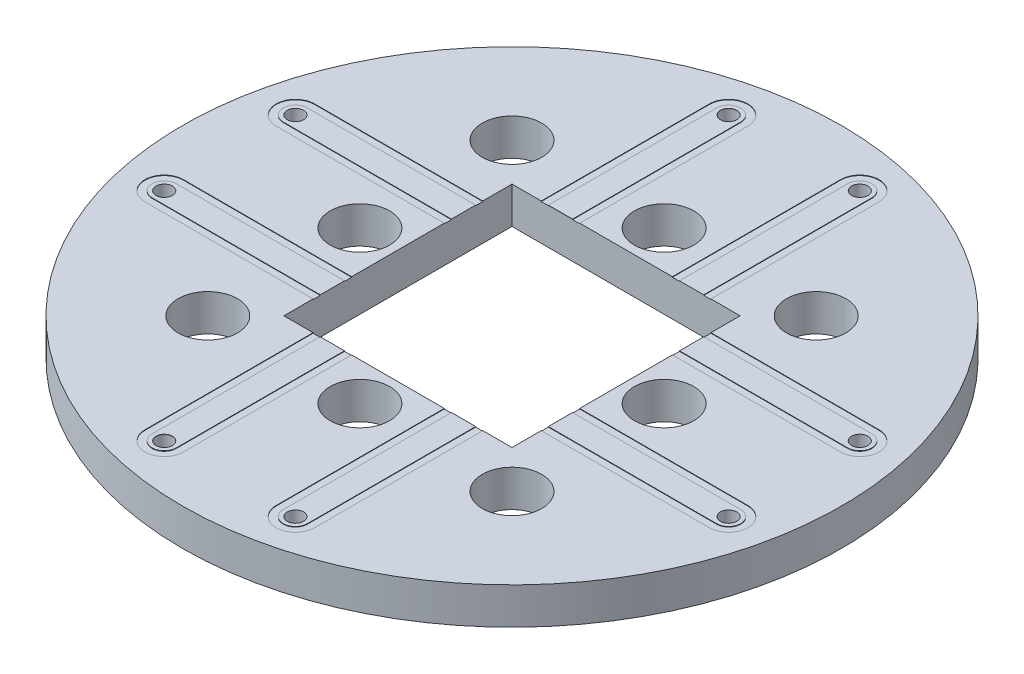
SolidWorks part; units mm, degrees
material "Ceramic Porcelain"
ref_plane "Front Plane" through (0, 0, 0) normal (0, 0, 1) x (1, 0, 0)
ref_plane "Top Plane" through (0, 0, 0) normal (0, 1, 0) x (1, 0, 0)
ref_plane "Right Plane" through (0, 0, 0) normal (1, 0, 0) x (0, 0, -1)
ref_axis "Y Axis" through (0, 0.0762, 0) along (0, -1, 0)
sketch "Boday Sketch" plane through (0, 0, 0) normal (0, 1, 0) x (1, 0, 0)
  circle A0 centre (0, 0) radius 11.557
  dimension "D1" = 23.114
extrude "Body" add sketch "Boday Sketch" against normal blind 1.27
sketch "Copper Sketch" plane through (0, 0, 0) normal (0, 1, 0) x (1, 0, 0)
  circle A0 centre (0, 0) radius 11.557
  dimension "D1" = 23.114
extrude "Copper" add sketch "Copper Sketch" along normal blind 0.0175
sketch "IO Hole Positions" plane through (0, 0, 0) normal (0, 1, 0) x (1, 0, 0)
  line L0 (-11.557, 0) -> (11.557, 0) construction
  circle A1 centre (0, 0) radius 11.557 construction
  point P1 (-2.3, 9.8962)
  point P8 (-2.3, -9.8962)
  dimension "D2" = 2.3
sketch "Gap" plane through (0, 0, 0) normal (0, 1, 0) x (1, 0, 0)
  line L10 (-2.975, 9.8962) -> (-2.975, -9.8962)
  line L11 (-11.557, 0) -> (11.557, 0) construction
  line L12 (-2.975, 0) -> (-1.625, 0) construction
  line L13 (-1.625, -9.8962) -> (-1.625, 9.8962)
  arc A5 (-1.625, 9.8962) -> (-2.975, 9.8962) centre (-2.3, 9.8962) ccw
  arc A6 (-1.625, -9.8962) -> (-2.975, -9.8962) centre (-2.3, -9.8962) cw
  dimension "D1" = 0.675
sketch "Center Sketch" plane through (0, 0, 0) normal (0, 1, 0) x (1, 0, 0)
  line L6 (-2.725, 9.8962) -> (-2.725, -9.8962)
  line L7 (-11.557, 0) -> (11.557, 0) construction
  line L8 (-2.725, 0) -> (-1.875, 0) construction
  line L9 (-1.875, -9.8962) -> (-1.875, 9.8962)
  arc A3 (-1.875, 9.8962) -> (-2.725, 9.8962) centre (-2.3, 9.8962) ccw
  arc A4 (-1.875, -9.8962) -> (-2.725, -9.8962) centre (-2.3, -9.8962) cw
  dimension "D1" = 0.425
extrude "Gap Cut" cut sketch "Gap" along normal through all
extrude "Center" add sketch "Center Sketch" along normal blind 0.0175 separate body
sketch "IO Hole Sketch" plane through (0, 0, 0) normal (0, 1, 0) x (1, 0, 0)
  circle A1 centre (-2.3, 9.8962) radius 0.287
  circle A3 centre (-2.3, -9.8962) radius 0.287
  dimension "D1" = 0.574
  dimension "D2" = 0.574
extrude "IO Hole" cut sketch "IO Hole Sketch" against normal through all and the other way through all
pattern_circular "Gap Cuts" count 4 over 360 about axis through (0, 0.0762, 0) along (0, -1, 0) of "Gap Cut"
pattern_circular "Centers" count 4 over 360 about axis through (0, 0.0762, 0) along (0, -1, 0) of "Center"
pattern_circular "IO Holes" count 4 over 360 about axis through (0, 0.0762, 0) along (0, -1, 0) of "IO Hole"
sketch "Pocket Sketch" plane through (0, 0, 0) normal (0, 1, 0) x (1, 0, 0)
  line L1 (-4, -4) -> (4, -4)
  line L2 (-4, -4) -> (-4, 4)
  line L3 (-4, 4) -> (4, 4)
  line L4 (4, -4) -> (4, 4)
  line L5 (-4, -4) -> (4, 4) construction
  line L6 (-4, 4) -> (4, -4) construction
  point P0 (0, 0)
  dimension "D1" = 8
  dimension "D2" = 8
extrude "Pocket" cut sketch "Pocket Sketch" against normal through all and the other way through all
sketch "Posts" plane through (0, 0, 0) normal (0, 1, 0) x (1, 0, 0)
  circle A0 centre (0, 5.334) radius 1.0414
  circle A8 centre (-5.334, 5.334) radius 1.0414
  point P0 (0, 5.334)
  point P4 (-5.334, 5.334)
  dimension "D2" = 2.0828
  dimension "D4" = 2.0828
  dimension "D1" = 5.334
  dimension "D3" = 7.5434
  dimension "D5" = 5.334
extrude "Post Cut" cut sketch "Posts" against normal through all and the other way through all
pattern_circular "Post Cuts" count 4 over 360 about axis through (0, 0.0762, 0) along (0, -1, 0) of "Post Cut"
equation "\"mount_d\"= 0.91in"
equation "\"dieletric_h\"= 0.05in"
equation "\"D1@Boday Sketch\" = \"mount_d\""
equation "\"D1@Body\" = \"dieletric_h\""
equation "\"screw_inner_r\"= 0.415in"
equation "\"io_r\"= 0.4in"
equation "\"io_hole_d\"= 0.574mm"
equation "\"W\"= 0.85mm"
equation "\"G\"= 0.25mm"
equation "\"copper_t\"= 17.5um"
equation "\"silicon_size\"= 8mm"
equation "\"D1@Center\" = \"copper_t\""
equation "\"D1@Copper\"=\"copper_t\""
equation "\"D1@Pocket Sketch\" = \"silicon_size\""
equation "\"D2@Pocket Sketch\" = \"silicon_size\""
equation "\"post_r1\" = 0.21in"
equation "\"post_r2\"= \"post_r1\" * sqr ( 2 )"
equation "\"D1@Posts\"=\"post_r1\""
equation "\"post_hole_size\" = 0.082in"
equation "\"D2@Posts\"=\"post_hole_size\""
equation "\"D3@Posts\"=\"post_r2\""
equation "\"D4@Posts\"=\"post_hole_size\""
equation "\"io_x\" = 2.3mm"
equation "\"D1@IO Hole Positions\"=\"io_r\""
equation "\"D2@IO Hole Positions\"=\"io_x\""
equation "\"D1@IO Hole Sketch\"=\"io_hole_d\""
equation "\"D2@IO Hole Sketch\"=\"io_hole_d\""
equation "\"D1@Gap\"= \"W\" / 2 + \"G\""
equation "\"D1@Center Sketch\"=\"W\" / 2"
equation "\"D5@Posts\"=\"post_r1\""
